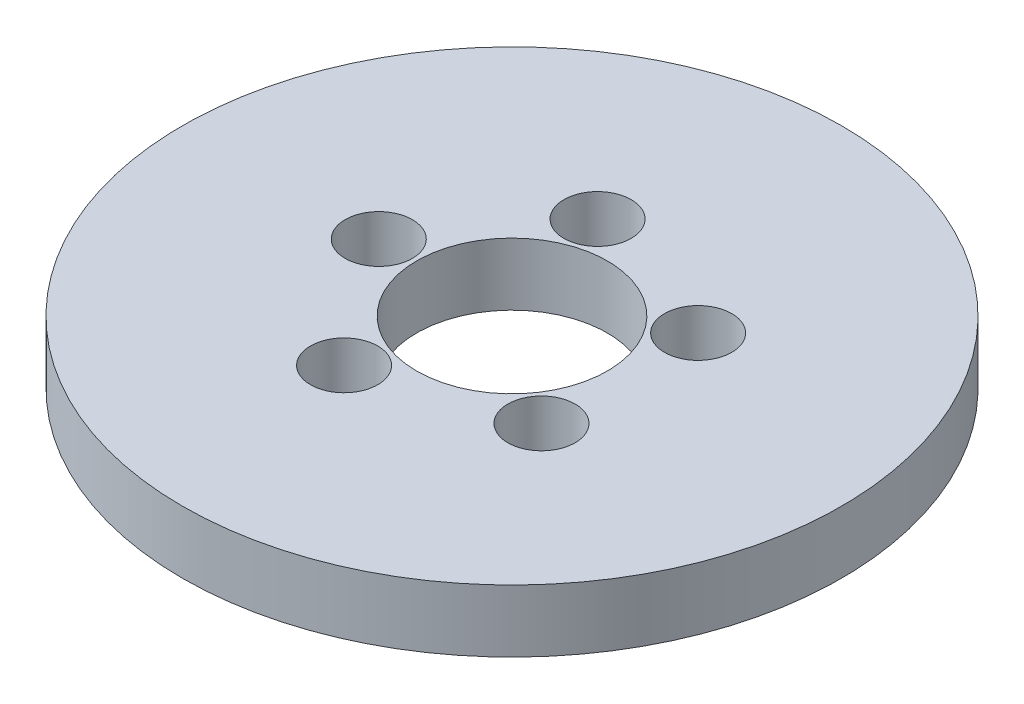
SolidWorks part; units mm, degrees
ref_plane "Front Plane" through (0, 0, 0) normal (0, 0, 1) x (1, 0, 0)
ref_plane "Top Plane" through (0, 0, 0) normal (0, 1, 0) x (1, 0, 0)
ref_plane "Right Plane" through (0, 0, 0) normal (1, 0, 0) x (0, 0, -1)
sketch "Sketch1" plane through (0, 0, 0) normal (0, 1, 0) x (1, 0, 0)
  circle A0 centre (0, 0) radius 95
  dimension "FLANGE_OD" = 190
extrude "Boss-Extrude1" add sketch "Sketch1" along normal blind 18
sketch "Sketch2" plane through (0, 0, 0) normal (0, 1, 0) x (1, 0, 0)
  circle A0 centre (0, 0) radius 27.5
  dimension "BORE_D" = 55
extrude "Cut-Extrude1" cut sketch "Sketch2" along normal through all
sketch "Sketch3" plane through (0, 18, 0) normal (0, 1, 0) x (1, 0, 0)
  circle A0 centre (0, 0) radius 38.4103 construction
  circle A1 centre (-38.4103, 0) radius 9.691
  dimension "BOLT_D" = 19.3819
  dimension "BOLT_PCD" = 76.8205
extrude "Cut-Extrude2" cut sketch "Sketch3" against normal blind 17.0771
pattern_circular "CirPattern1" count 5 over 360 about axis through (0, 0, 0) along (0, 1, 0) of "Cut-Extrude2"
